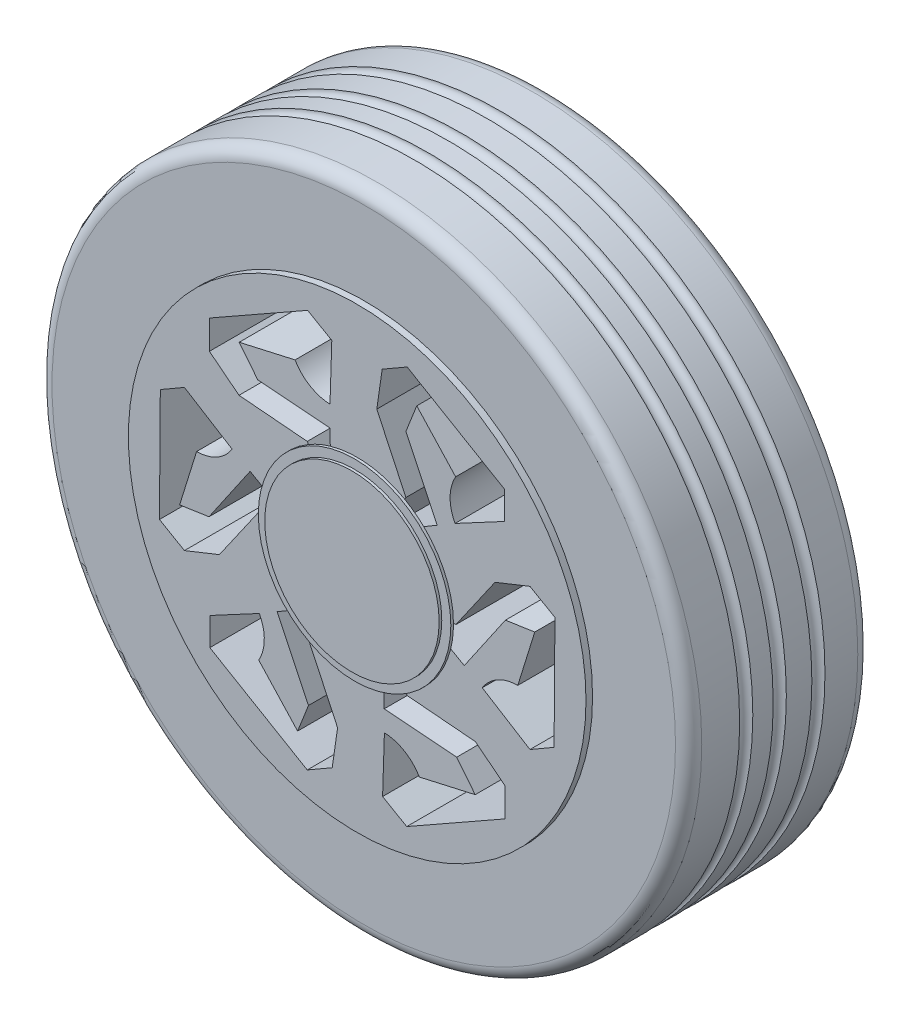
SolidWorks part; units mm, degrees
ref_plane "Front Plane" through (0, 0, 0) normal (0, 0, 1) x (1, 0, 0)
ref_plane "Top Plane" through (0, 0, 0) normal (0, 1, 0) x (1, 0, 0)
ref_plane "Right Plane" through (0, 0, 0) normal (1, 0, 0) x (0, 0, -1)
sketch "Sketch2" plane through (0, 0, 0) normal (0, 0, 1) x (1, 0, 0)
  circle A0 centre (0, 0) radius 247.55
  dimension "D1" = 495.1
extrude "Boss-Extrude1" add sketch "Sketch2" along normal blind 138.9
sketch "Sketch3" plane through (0, 0, 138.9) normal (0, 0, 1) x (1, 0, 0)
  circle A0 centre (0, 0) radius 174.35
  dimension "D1" = 348.7
fillet "Fillet1" radius 10 1 edges at (247.55, 0, 138.9)
fillet "Fillet2" radius 10 1 edges at (247.55, 0, 0)
extrude "Boss-Extrude2" add sketch "Sketch3" along normal blind 5
sketch "Sketch5" plane through (0, 0, 143.9) normal (0, 0, 1) x (1, 0, 0)
  line L0 (105.0037, 43.3694) -> (131.6337, 54.0214)
  line L1 (131.6337, 54.0214) -> (150.6653, 43.0319)
  line L2 (150.6653, 43.0319) -> (150.3446, -0.3609)
  line L3 (150.3446, -0.3609) -> (150.0291, -43.0412)
  line L4 (150.0291, -43.0412) -> (131.6404, -53.6579)
  line L5 (131.6404, -53.6579) -> (95.2902, -31.0843)
  line L7 (122.3632, -15.976) -> (135.2996, 25.6977)
  line L8 (135.2996, 25.6977) -> (112.9256, 22.3447)
  line L10 (112.9256, 22.3447) -> (81.5922, -23.3101)
  line L11 (81.5922, -23.3101) -> (40.2577, 0.1488)
  line L12 (40.2577, 0.1488) -> (75.1777, 0.5509)
  line L13 (75.1777, 0.5509) -> (105.0037, 43.3694)
  line L14 (90.0609, -69.2512) -> (112.6007, -86.9874)
  line L16 (112.6007, -86.9874) -> (112.5994, -108.964)
  line L17 (112.5994, -108.964) -> (74.8597, -130.3827)
  line L18 (74.8597, -130.3827) -> (37.7398, -151.4496)
  line L19 (37.7398, -151.4496) -> (19.3511, -140.8329)
  line L20 (19.3511, -140.8329) -> (20.7253, -98.0659)
  line L21 (47.346, -113.9577) -> (89.9046, -104.3241)
  line L22 (89.9046, -104.3241) -> (75.8138, -86.6241)
  line L23 (19.0329, 141.0088) -> (38.0659, 151.9959)
  line L24 (38.0659, 151.9959) -> (75.4849, 130.0217)
  line L25 (75.4849, 130.0217) -> (112.2893, 108.4084)
  line L26 (112.2893, 108.4084) -> (112.2893, 87.175)
  line L27 (112.2893, 87.175) -> (74.5649, 66.9816)
  line L28 (75.0173, 97.9817) -> (45.395, 130.0217)
  line L29 (45.395, 130.0217) -> (37.1117, 108.9688)
  line L30 (37.1117, 108.9688) -> (60.9833, 59.0059)
  line L31 (60.9833, 59.0059) -> (20, 34.9386)
  line L32 (20, 34.9386) -> (37.1117, 65.3813)
  line L33 (37.1117, 65.3813) -> (14.9428, 112.6206)
  line L34 (14.9428, 112.6206) -> (19.0329, 141.0088)
  line L35 (75.8138, -86.6241) -> (20.6089, -82.316)
  line L36 (20.6089, -82.316) -> (20.2577, -34.7898)
  line L37 (20.2577, -34.7898) -> (38.066, -64.8303)
  line L38 (38.066, -64.8303) -> (90.0609, -69.2512)
  line L39 (-14.9428, -112.6206) -> (-19.0329, -141.0088)
  line L40 (-19.0329, -141.0088) -> (-38.0659, -151.9959)
  line L41 (-38.0659, -151.9959) -> (-75.4849, -130.0217)
  line L42 (-75.4849, -130.0217) -> (-112.2893, -108.4084)
  line L43 (-112.2893, -108.4084) -> (-112.2893, -87.175)
  line L44 (-112.2893, -87.175) -> (-74.5649, -66.9816)
  line L45 (-75.0173, -97.9817) -> (-45.395, -130.0217)
  line L46 (-45.395, -130.0217) -> (-37.1117, -108.9687)
  line L47 (-37.1117, -108.9687) -> (-60.9833, -59.0059)
  line L48 (-60.9833, -59.0059) -> (-20, -34.9386)
  line L49 (-20, -34.9386) -> (-37.1117, -65.3812)
  line L50 (-37.1117, -65.3812) -> (-14.9428, -112.6206)
  line L51 (-105.0037, -43.3694) -> (-131.6337, -54.0214)
  line L52 (-131.6337, -54.0214) -> (-150.6653, -43.0319)
  line L53 (-150.6653, -43.0319) -> (-150.3446, 0.3609)
  line L54 (-150.3446, 0.3609) -> (-150.0291, 43.0412)
  line L55 (-150.0291, 43.0412) -> (-131.6404, 53.6579)
  line L56 (-131.6404, 53.6579) -> (-95.2902, 31.0843)
  line L57 (-122.3632, 15.976) -> (-135.2996, -25.6977)
  line L58 (-135.2996, -25.6977) -> (-112.9256, -22.3447)
  line L59 (-112.9256, -22.3447) -> (-81.5922, 23.3101)
  line L60 (-81.5922, 23.3101) -> (-40.2577, -0.1488)
  line L61 (-40.2577, -0.1488) -> (-75.1777, -0.5509)
  line L62 (-75.1777, -0.5509) -> (-105.0037, -43.3694)
  line L63 (-90.0609, 69.2512) -> (-112.6007, 86.9874)
  line L64 (-112.6007, 86.9874) -> (-112.5994, 108.964)
  line L65 (-112.5994, 108.964) -> (-74.8597, 130.3827)
  line L66 (-74.8597, 130.3827) -> (-37.7398, 151.4496)
  line L67 (-37.7398, 151.4496) -> (-19.3511, 140.8329)
  line L68 (-19.3511, 140.8329) -> (-20.7253, 98.0659)
  line L69 (-47.346, 113.9577) -> (-89.9046, 104.3241)
  line L70 (-89.9046, 104.3241) -> (-75.8138, 86.6241)
  line L71 (-75.8138, 86.6241) -> (-20.6089, 82.316)
  line L72 (-20.6089, 82.316) -> (-20.2577, 34.7898)
  line L73 (-20.2577, 34.7898) -> (-38.066, 64.8303)
  line L74 (-38.066, 64.8303) -> (-90.0609, 69.2512)
  arc A2 (74.5649, 66.9816) -> (75.0173, 97.9817) centre (102.7589, 82.0735) cw
  arc A3 (95.2902, -31.0843) -> (122.3632, -15.976) centre (122.4571, -47.955) cw
  arc A4 (20.7253, -98.0659) -> (47.346, -113.9577) centre (19.6983, -130.0285) cw
  arc A5 (-74.5649, -66.9816) -> (-75.0173, -97.9817) centre (-102.7589, -82.0735) cw
  arc A6 (-95.2902, 31.0843) -> (-122.3632, 15.976) centre (-122.4571, 47.955) cw
  arc A7 (-20.7253, 98.0659) -> (-47.346, 113.9577) centre (-19.6983, 130.0285) cw
  point P87 (0, 0)
  dimension "D1" = 6
sketch "Sketch6" plane through (0, 0, 143.9) normal (0, 0, 1) x (1, 0, 0)
sketch "Sketch8" plane through (0, 0, 143.9) normal (0, 0, 1) x (1, 0, 0)
extrude "Cut-Extrude1" cut sketch "Sketch5" against normal blind 178
sketch "Sketch9" plane through (0, 0, 143.9) normal (0, 0, 1) x (1, 0, 0)
  circle A0 centre (0, 0) radius 73.3512
extrude "Boss-Extrude3" add sketch "Sketch9" along normal blind 2
sketch "Sketch10" plane through (0, 0, 145.9) normal (0, 0, 1) x (1, 0, 0)
  circle A0 centre (0, 0) radius 66.4494
extrude "Boss-Extrude4" add sketch "Sketch10" along normal blind 2
sketch3d "3DSketch1" plane through (0, 0, 0) normal (0, 0, 1) x (1, 0, 0)
sketch3d "3DSketch2" plane through (0, 0, 0) normal (0, 0, 1) x (1, 0, 0)
sketch "Sketch14" plane through (0, 0, 95) normal (0, 0, 1) x (1, 0, 0)
  circle A0 centre (0, 0) radius 247.55
sketch "Sketch15" plane through (0, 0, 69.45) normal (0, 0, 1) x (1, 0, 0)
  circle A0 centre (0, 0) radius 247.55
sketch "Sketch16" plane through (0, 0, 40) normal (0, 0, 1) x (1, 0, 0)
  circle A0 centre (0, 0) radius 247.55
sketch3d "3DSketch3" plane through (0, 0, 0) normal (0, 0, 1) x (1, 0, 0)
sweep "Cut-Sweep1" cut path "Sketch16" circular profile diameter 10 parameters "D3"=10
sweep "Cut-Sweep2" cut path "Sketch15" circular profile diameter 10 parameters "D3"=10
sweep "Cut-Sweep3" cut path "Sketch14" circular profile diameter 10 parameters "D3"=10
sketch3d "3DSketch4"
  circle A0 centre (0, 0, 0) radius 65.4119
  point P2 (0, 0, 65.4119)
  point P4 (0, 0, 0)
